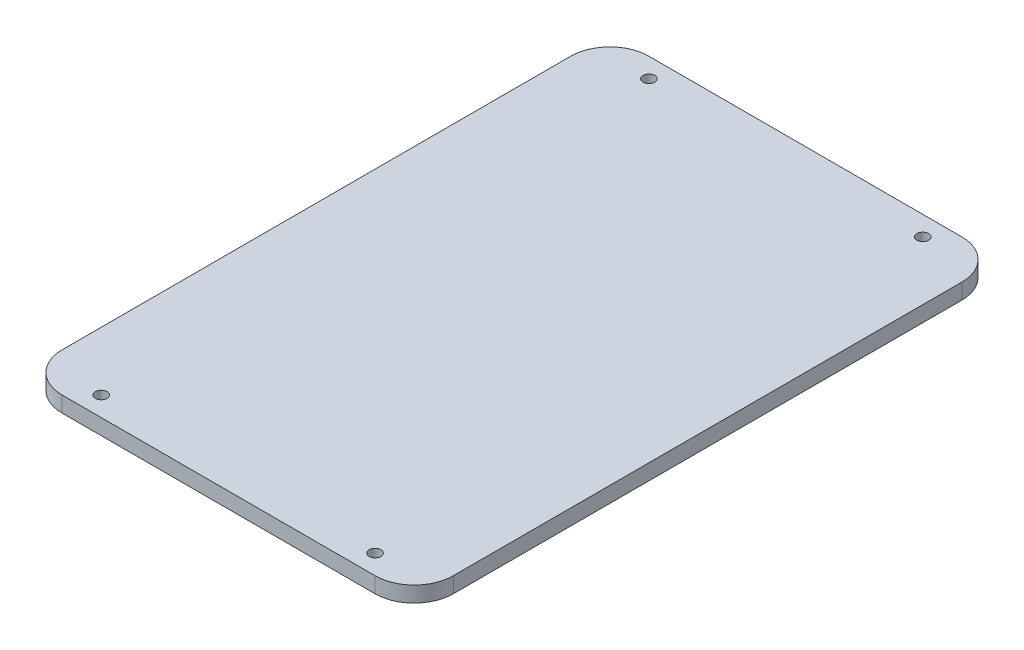
SolidWorks part; units mm, degrees
ref_plane "前视基准面" through (0, 0, 0) normal (0, 0, 1) x (1, 0, 0)
ref_plane "上视基准面" through (0, 0, 0) normal (0, 1, 0) x (1, 0, 0)
ref_plane "右视基准面" through (0, 0, 0) normal (1, 0, 0) x (0, 0, -1)
other "Configuration Table"
sketch "草图1" plane through (0, 0, 0) normal (0, 1, 0) x (1, 0, 0)
  line L0 (0, 119.0805) -> (0, -123.6398) construction
  line L1 (-50, -75) -> (50, -75)
  line L2 (-50, -75) -> (-50, 75)
  line L3 (-50, 75) -> (50, 75)
  line L4 (50, -75) -> (50, 75)
  line L5 (-50, -75) -> (50, 75) construction
  line L6 (-50, 75) -> (50, -75) construction
  line L7 (-120.6897, 0) -> (123.1034, 0) construction
  circle A0 centre (35, 70) radius 1.5
  circle A1 centre (-35, 70) radius 1.5
  circle A2 centre (-35, -70) radius 1.5
  circle A3 centre (35, -70) radius 1.5
  point P0 (0, 0)
  point P12 (123.1034, 0)
  dimension "D1" = 140
  dimension "D2" = 70
  dimension "D5" = 3
  dimension "D3" = 100
  dimension "D4" = 150
extrude "凸台-拉伸1" add sketch "草图1" along normal blind 4
fillet "圆角1" radius 10 4 edges at (-50, 2, 75) (-50, 2, -75) (50, 2, -75) (50, 2, 75)
